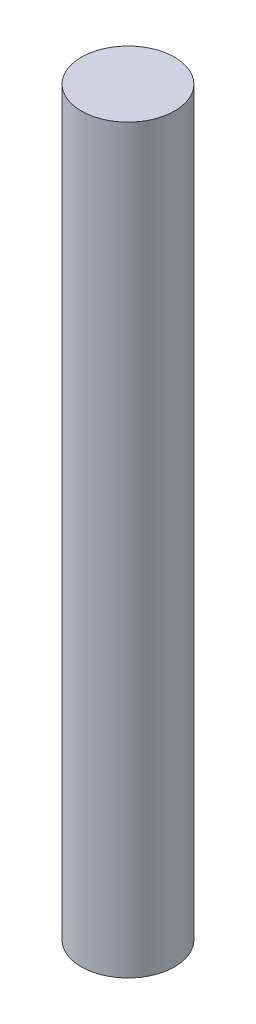
SolidWorks part; units mm, degrees
ref_plane "Front Plane" through (0, 0, 0) normal (0, 0, 1) x (1, 0, 0)
ref_plane "Top Plane" through (0, 0, 0) normal (0, 1, 0) x (1, 0, 0)
ref_plane "Right Plane" through (0, 0, 0) normal (1, 0, 0) x (0, 0, -1)
sketch "Sketch1" plane through (0, 0, 0) normal (0, 1, 0) x (1, 0, 0)
  circle A0 centre (0, 0) radius 3.175
  dimension "D1" = 6.35
sketch "Sketch2" plane through (0, 0, 0) normal (1, 0, 0) x (0, 0, -1)
  line L0 (0, 0) -> (0, 50.456)
  circle A0 centre (0, 0) radius 50.456 construction
extrude "Boss-Extrude1" add sketch "Sketch1" along normal up to vertex (50.456 mm away) contours A0 up to point (0, 50.456, 0)
